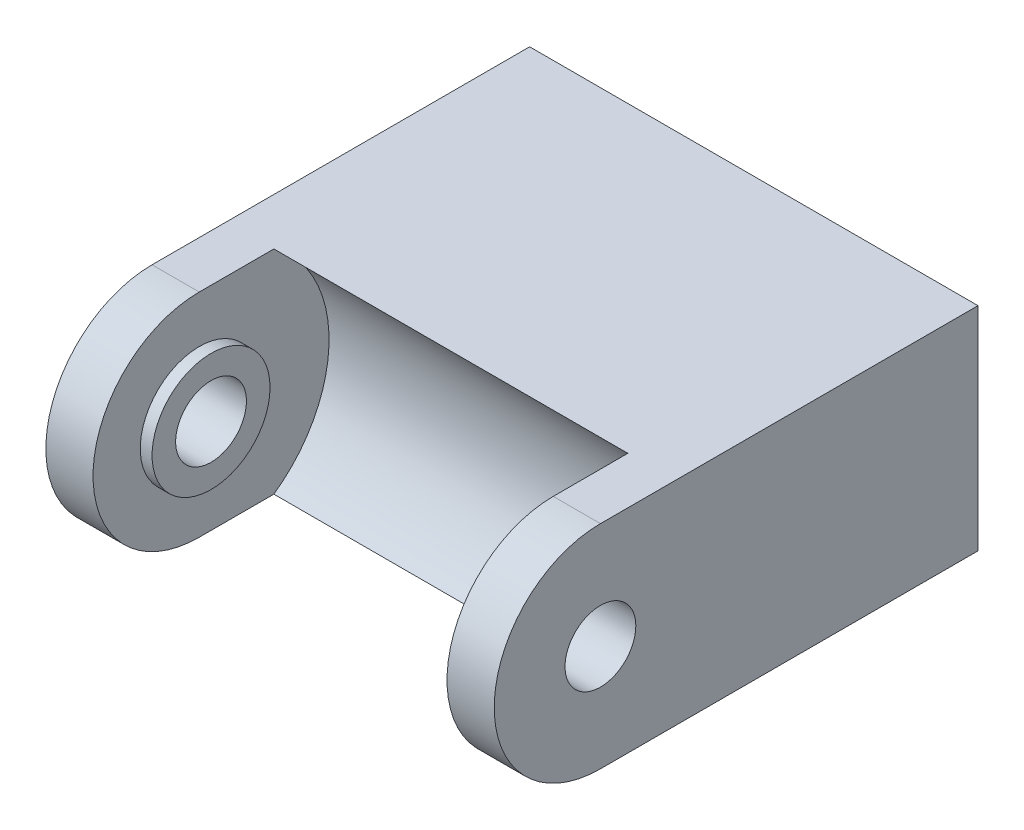
SolidWorks part; units mm, degrees
ref_plane "Front" through (0, 0, 0) normal (0, 0, 1) x (1, 0, 0)
ref_plane "Top" through (0, 0, 0) normal (0, 1, 0) x (1, 0, 0)
ref_plane "Right" through (0, 0, 0) normal (1, 0, 0) x (0, 0, -1)
sketch "Эскиз1" plane through (0, 0, 0) normal (1, 0, 0) x (0, 0, -1)
  line L0 (0, 4.5) -> (16, 4.5)
  line L1 (16, 4.5) -> (16, -4.5)
  line L2 (16, -4.5) -> (0, -4.5)
  circle A0 centre (0, 0) radius 4.5
  dimension "D1" = 9
  dimension "D2" = 16
extrude "Бобышка-Вытянуть1" add sketch "Эскиз1" along normal blind 9.5 and the other way blind 9.5 contours A0 | A0 L2 L1 L0 region at (0, 0, -9.7267) region at (0, 0, 0)
sketch "Эскиз2" plane through (0, 0, 0) normal (1, 0, 0) x (0, 0, -1)
  circle A0 centre (0, 0) radius 5.5
extrude "Вырез-Вытянуть1" cut sketch "Эскиз2" against normal blind 7 and the other way blind 7
sketch "Эскиз3" plane through (0, 0, 0) normal (1, 0, 0) x (0, 0, -1)
  circle A0 centre (0, 0) radius 1.5
extrude "Вырез-Вытянуть2" cut sketch "Эскиз3" against normal through all both and the other way through all
sketch "Эскиз4" plane through (0, 0, 0) normal (1, 0, 0) x (0, 0, -1)
  circle A0 centre (0, 0) radius 5.5
  circle A1 centre (0, 0) radius 2.5
  dimension "D1" = 5
  dimension "D2" = 11
extrude "Вырез-Вытянуть3" cut sketch "Эскиз4" against normal blind 7.5 and the other way blind 7.5
sketch "Эскиз5" plane through (0, 0, -16) normal (0, 0, -1) x (-1, 0, 0)
  circle A0 centre (0, 0) radius 1.75
extrude "Вырез-Вытянуть4" cut sketch "Эскиз5" against normal blind 2
